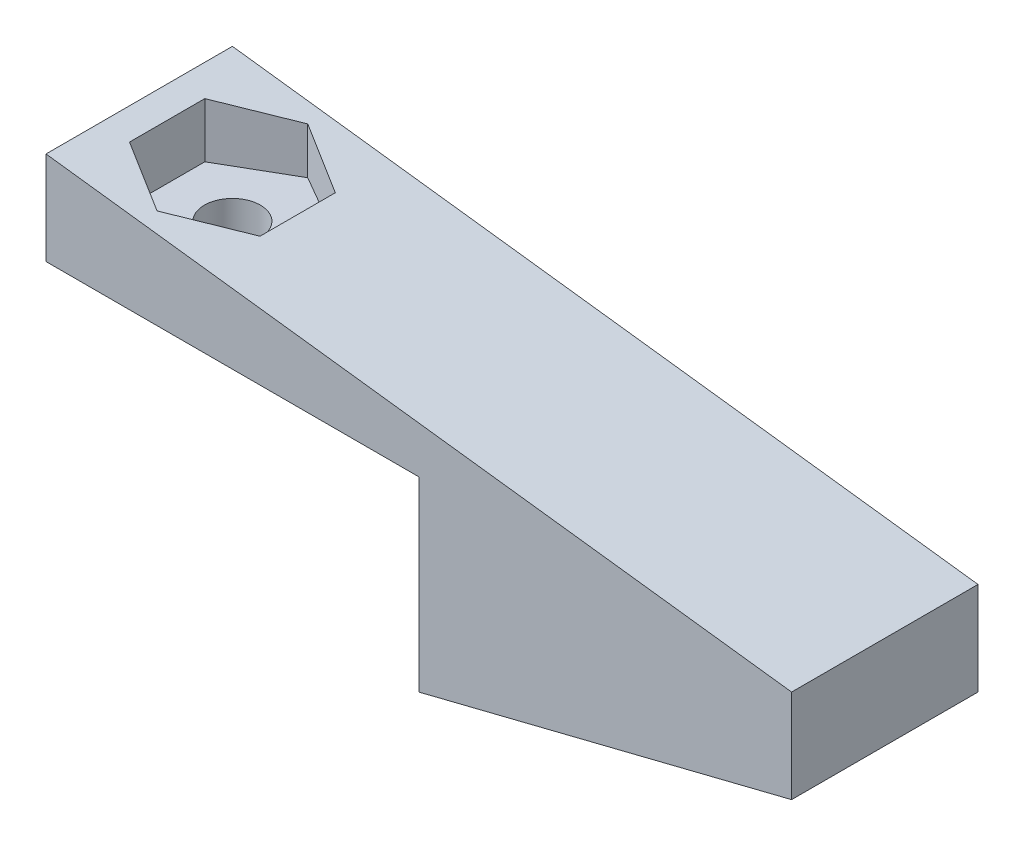
SolidWorks part; units mm, degrees
ref_plane "Front Plane" through (0, 0, 0) normal (0, 0, 1) x (1, 0, 0)
ref_plane "Top Plane" through (0, 0, 0) normal (0, 1, 0) x (1, 0, 0)
ref_plane "Right Plane" through (0, 0, 0) normal (1, 0, 0) x (0, 0, -1)
sketch "Sketch1" plane through (0, 0, 0) normal (0, 0, 1) x (1, 0, 0)
  line L0 (0, 0) -> (0, 6.35)
  line L1 (0, 6.35) -> (50.8, 0)
  line L2 (50.8, 0) -> (50.8, -6.35)
  line L3 (50.8, -6.35) -> (25.4, -12.7)
  line L4 (25.4, -12.7) -> (25.4, 0)
  line L5 (25.4, 0) -> (0, 0)
  point P3 (50.8, 3.4231)
  point P8 (50.8, -7.3182)
  dimension "D1" = 6.35
  dimension "D2" = 50.8
  dimension "D3" = 25.4
  dimension "D4" = 12.7
  dimension "D5" = 6.35
extrude "Boss-Extrude1" add sketch "Sketch1" along normal mid plane 12.7
sketch "Sketch2" plane through (0, 0, 0) normal (0, -1, 0) x (-1, 0, 0)
  line L0 (0, -6.35) -> (0, 6.35) construction
  line L1 (-10.4775, 0) -> (10.4775, 0) construction
  circle A0 centre (-6.35, 0) radius 1.905
  point P4 (-6.35, -2.0996)
  point P5 (0, 0)
  dimension "D1" = 3.81
  dimension "D2" = 6.35
extrude "Cut-Extrude1" cut sketch "Sketch2" against normal up to next
sketch "Sketch3" plane through (0, 0, 0) normal (0, -1, 0) x (1, 0, 0)
  line L1 (6.35, 5.1326) -> (1.905, 2.5663)
  line L2 (1.905, 2.5663) -> (1.905, -2.5663)
  line L3 (1.905, -2.5663) -> (6.35, -5.1326)
  line L4 (6.35, -5.1326) -> (10.795, -2.5663)
  line L5 (10.795, -2.5663) -> (10.795, 2.5663)
  line L6 (10.795, 2.5663) -> (6.35, 5.1326)
  circle A0 centre (6.35, 0) radius 4.445 construction
  dimension "D1" = 8.89
extrude "Cut-Extrude2" cut sketch "Sketch3" against normal up to next from offset 2.3813 offset against normal yes
sketch "Sketch4" plane through (25.4, 0, 0) normal (-1, 0, 0) x (0, 0, 1)
  line L0 (6.35, 0) -> (-6.35, 0) construction
  circle A0 centre (0, -7.62) radius 1.905
  point P4 (0, 0)
  dimension "D2" = 3.81
  dimension "D1" = 7.62
extrude "Cut-Extrude3" cut sketch "Sketch4" against normal blind 15.875
